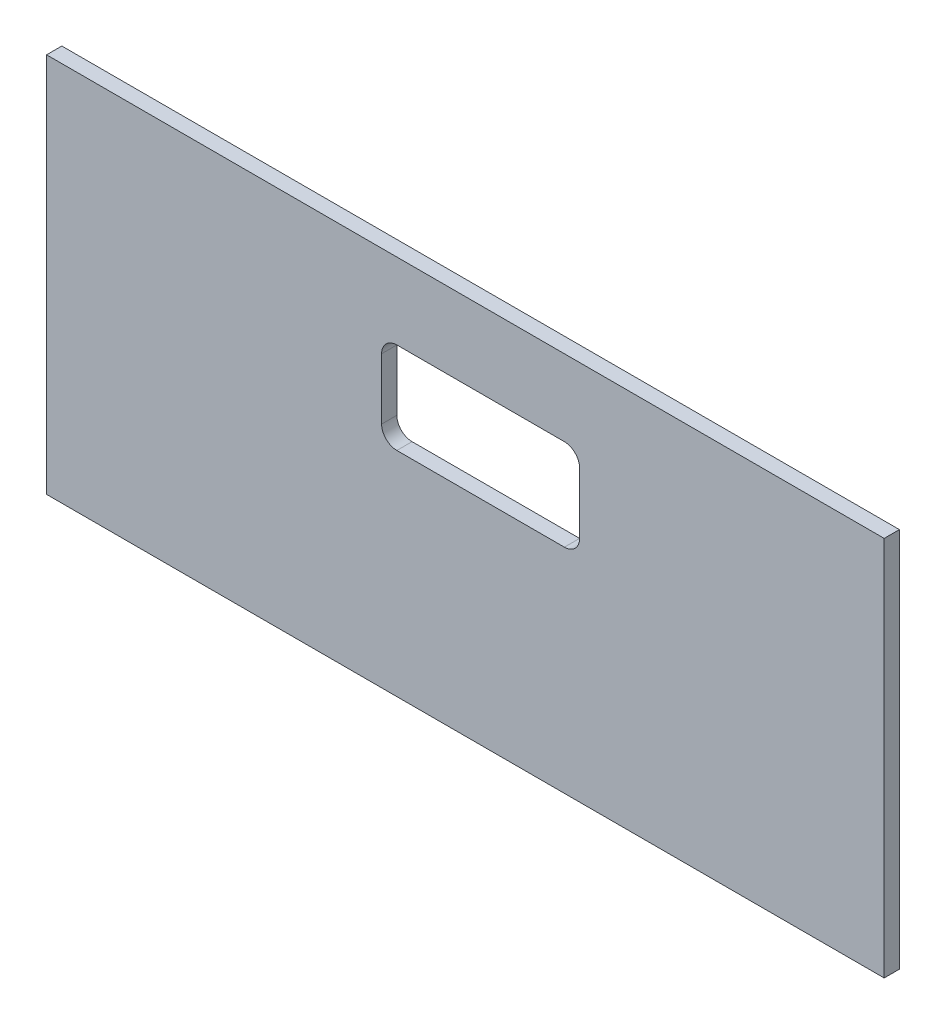
SolidWorks part; units mm, degrees
ref_plane "Front Plane" through (0, 0, 0) normal (0, 0, 1) x (1, 0, 0)
ref_plane "Top Plane" through (0, 0, 0) normal (0, 1, 0) x (1, 0, 0)
ref_plane "Right Plane" through (0, 0, 0) normal (1, 0, 0) x (0, 0, -1)
sketch "Sketch1" plane through (0, 0, 0) normal (0, 0, 1) x (1, 0, 0)
  line L1 (-27.5, -12.5) -> (27.5, -12.5)
  line L2 (-27.5, -12.5) -> (-27.5, 12.5)
  line L3 (-27.5, 12.5) -> (27.5, 12.5)
  line L4 (27.5, -12.5) -> (27.5, 12.5)
  line L5 (-27.5, -12.5) -> (27.5, 12.5) construction
  line L6 (-27.5, 12.5) -> (27.5, -12.5) construction
  point P0 (0, 0)
  dimension "D1" = 55
  dimension "D2" = 25
extrude "Boss-Extrude1" add sketch "Sketch1" along normal blind 1
sketch "Sketch2" plane through (0, 0, 1) normal (0, 0, 1) x (1, 0, 0)
  line L0 (27.5, -12.5) -> (27.5, 12.5) construction
  line L1 (-5.5, 7.5) -> (7.5, 7.5)
  line L2 (-5.5, 7.5) -> (-5.5, 1.5)
  line L3 (-5.5, 1.5) -> (7.5, 1.5)
  line L4 (7.5, 7.5) -> (7.5, 1.5)
  line L5 (-27.5, -12.5) -> (27.5, -12.5) construction
  dimension "D1" = 13
  dimension "D2" = 6
  dimension "D3" = 33
  dimension "D4" = 20
extrude "Cut-Extrude1" cut sketch "Sketch2" against normal through all both and the other way through all
fillet "Fillet1" radius 1 4 edges at (-5.5, 1.5, 0.5) (7.5, 1.5, 0.5) (7.5, 7.5, 0.5) (-5.5, 7.5, 0.5)
